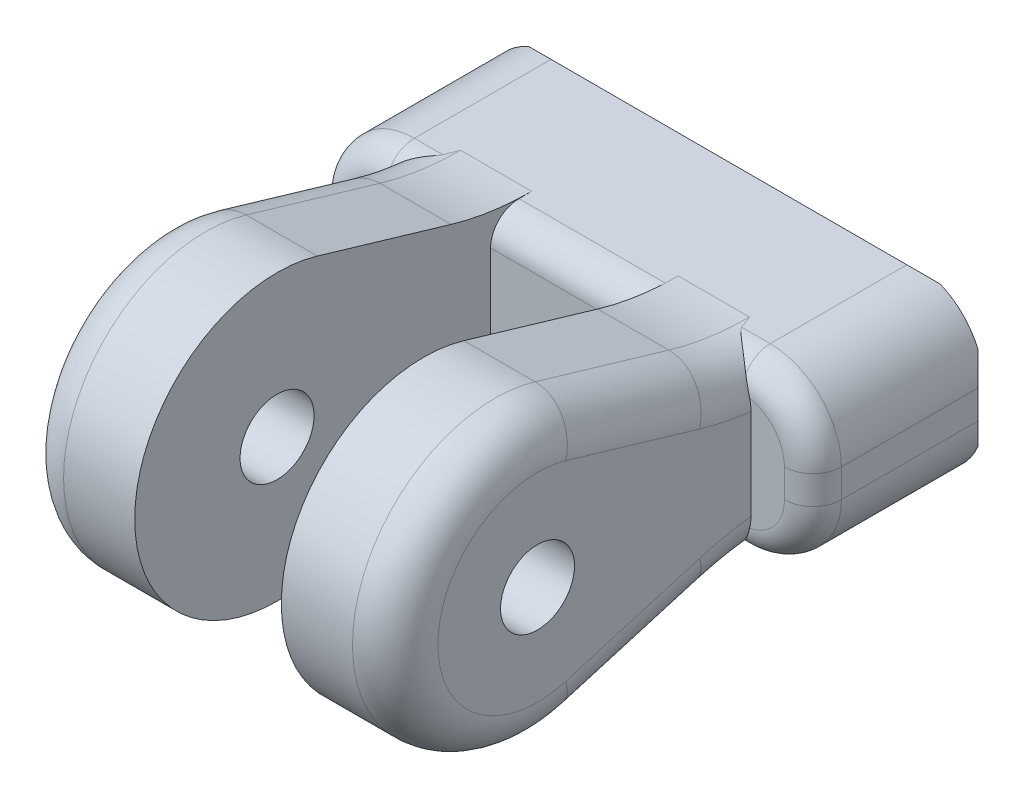
SolidWorks part; units mm, degrees
ref_plane "Front Plane" through (0, 0, 0) normal (0, 0, 1) x (1, 0, 0)
ref_plane "Top Plane" through (0, 0, 0) normal (0, 1, 0) x (1, 0, 0)
ref_plane "Right Plane" through (0, 0, 0) normal (1, 0, 0) x (0, 0, -1)
sketch "Sketch1" plane through (0, 0, 0) normal (0, 0, 1) x (1, 0, 0)
  line L0 (0, 0) -> (0, 31.117) construction
  line L4 (-17.5, -6) -> (17.5, -6)
  line L5 (-17.5, -6) -> (-17.5, 6)
  line L6 (-17.5, 6) -> (17.5, 6)
  line L7 (17.5, -6) -> (17.5, 6)
  line L8 (-17.5, -6) -> (17.5, 6) construction
  line L9 (-17.5, 6) -> (17.5, -6) construction
  circle A0 centre (11, 0) radius 4.05
  circle A1 centre (-11, 0) radius 4.05
  dimension "D1" = 8.1
  dimension "D3" = 12
  dimension "D2" = 22
  dimension "D4" = 35
extrude "Boss-Extrude1" add sketch "Sketch1" along normal mid plane 12
sketch "Sketch5" plane through (0, 0, 6) normal (0, 0, 1) x (1, 0, 0)
  circle A0 centre (-11, 0) radius 4.05
  circle A1 centre (-11, 0) radius 4.05 construction
  circle A2 centre (11, 0) radius 4.05
  circle A3 centre (11, 0) radius 4.05 construction
extrude "Boss-Extrude3" add sketch "Sketch5" against normal blind 3
sketch "Sketch6" plane through (0, 0, 0) normal (1, 0, 0) x (0, 0, -1)
  line L0 (-6, 6) -> (-18.1698, 9.5911)
  line L1 (0, 0) -> (16.6175, 0) construction
  line L2 (-6, -6) -> (-18.1698, -9.5911)
  line L3 (-6, 6) -> (-6, -6)
  circle A0 centre (-21, 0) radius 10
  circle A1 centre (-21, 0) radius 2.6
  dimension "D1" = 20
  dimension "D3" = 5.2
  dimension "D2" = 21
extrude "Boss-Extrude4" add sketch "Sketch6" along normal blind 8 from offset 5.15 contours A0 L2 L3 L0 | A0 A1 region at (0, 0, 9.5342) region at (0, 5.818, 13.2171)
mirror "Mirror2" about plane through (0, 0, 0) normal (1, 0, 0) of "Boss-Extrude4"
fillet "Fillet1" radius 20 4 edges at (-9.15, -6, 6) (9.15, -6, 6) (-9.15, 6, 6) (9.15, 6, 6)
fillet "Fillet2" radius 3 10 edges at (-13.15, -8.2044, 13.4705) (-13.15, 0, 31) (13.15, -8.2044, 13.4705) (13.15, 0, 31) (-13.15, 8.2044, 13.4705) (13.15, 8.2044, 13.4705) (-13.15, 6.2055, 5.9703) (-13.15, -6.2055, 5.9703) (13.15, 6.2055, 5.9703) (13.15, -6.2055, 5.9703)
chamfer "Chamfer1" distance 0.4 angle 45 6 edges at (-15.05, 0, -6) (0, -6, -6) (17.5, 0, -6) (0, 6, -6) (-17.5, 0, -6) (15.05, 0, -6)
fillet "Fillet3" radius 5 4 edges at (17.5, -6, 0.2) (17.5, 6, 0.2) (-17.5, -6, 0.2) (-17.5, 6, 0.2)
fillet "Fillet4" radius 2 12 edges at (11.8733, -6, 6) (16.0355, -4.5355, 6) (17.5, 0, 6) (11.8733, 6, 6) (-11.8733, 6, 6) (-11.8733, -6, 6) (-16.0355, -4.5355, 6) (-17.5, 0, 6) (0, -6, 6) (0, 6, 6) (16.0355, 4.5355, 6) (-16.0355, 4.5355, 6)
